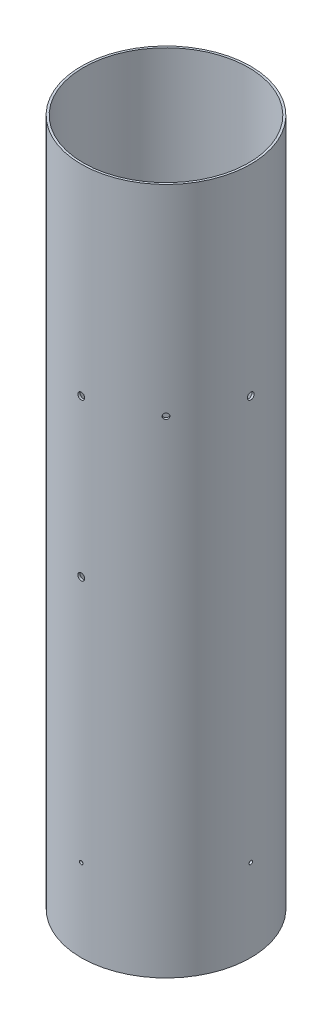
SolidWorks part; units mm, degrees
ref_plane "Front Plane" through (0, 0, 0) normal (0, 0, 1) x (1, 0, 0)
ref_plane "Top Plane" through (0, 0, 0) normal (0, 1, 0) x (1, 0, 0)
ref_plane "Right Plane" through (0, 0, 0) normal (1, 0, 0) x (0, 0, -1)
sketch "Sketch2" plane through (0, 0, 0) normal (0, 1, 0) x (1, 0, 0)
  circle A0 centre (0, 0) radius 76.3651
  circle A1 centre (0, 0) radius 78.359
  dimension "D1" = 152.7302
  dimension "D2" = 156.718
extrude "Boss-Extrude1" add sketch "Sketch2" along normal blind 635
sketch "Sketch3" plane through (0, 0, 0) normal (0, 0, 1) x (1, 0, 0)
  circle A0 centre (0, 76.2) radius 1.1906
  dimension "D2" = 2.3813
  dimension "D1" = 76.2
extrude "Cut-Extrude1" [suppressed] cut sketch "Sketch3" against normal through all both and the other way through all
pattern_circular "CirPattern1" [suppressed] count 4 over 360 of bodies 102
sketch "Sketch4" plane through (0, 0, 0) normal (0, 0, 1) x (1, 0, 0)
  circle A0 centre (0, 449.5038) radius 3.175
  dimension "D2" = 6.35
  dimension "D1" = 449.5038
extrude "Cut-Extrude2" cut sketch "Sketch4" against normal through all both and the other way through all
pattern_circular "CirPattern2" count 4 over 360 about axis through (0, 635, 0) along (0, 1, 0) of "Cut-Extrude2"
ref_plane "Plane1" through (55.4082, 0, 55.4082) normal (0.7071, 0, 0.7071) x (0, -1, 0)
sketch "Sketch5" plane through (55.4082, 0, 55.4082) normal (0.7071, 0, 0.7071) x (0, -1, 0)
  circle A0 centre (-449.5038, 0) radius 2.5794
  dimension "D1" = 5.1587
  dimension "D2" = 449.5038
extrude "Cut-Extrude3" cut sketch "Sketch5" against normal up to surface and the other way through all up to face at (-76.3025, 448.7766, 3.0906)
sketch "Sketch6" plane through (0, 0, 0) normal (0, 0, 1) x (1, 0, 0)
  circle A0 centre (0, 304.8) radius 3.175
  dimension "D2" = 304.8
extrude "Cut-Extrude4" cut sketch "Sketch6" against normal through all both and the other way through all
ref_plane "Plane2" through (0, 0, 78.359) normal (0, 0, 1) x (1, 0, 0)
sketch "Sketch7" plane through (0, 0, 78.359) normal (0, 0, 1) x (1, 0, 0)
  point P0 (0, 76.2)
  dimension "D1" = 76.2
hole_wizard "#4 Clearance Hole1" positions "Sketch7" profile "Sketch8" hole size "#4" standard "ANSI Inch"
sketch "Sketch8" plane through (0, 76.2, 78.359) normal (1, 0, 0) x (0, -1, 0)
  line L0 (0, 0) -> (0, 5.8066)
  line L1 (0, 5.8066) -> (1.6319, 4.826)
  line L2 (1.6319, 4.826) -> (1.6319, 0)
  line L5 (1.6319, 0) -> (0, 0)
  line L10 (0, 5.8066) -> (-1.632, 4.826) construction
  line L11 (0, -6.35) -> (0, 107.95) construction
  dimension "Hole Dia." = 3.2639
  dimension "Hole Depth" = 4.826
  dimension "Drill Angle" = 118
pattern_circular "CirPattern3" count 4 every 90 about axis through (0, 0, 0) along (0, 1, 0) of "#4 Clearance Hole1"
equation "\"Shear Pin Dia\"= 3 / 32"
equation "\"Shear Pin Offset\"= 3"
equation "\"D1@Sketch3\"=\"Shear Pin Offset\""
equation "\"D2@Sketch3\"=\"Shear Pin Dia\""
equation "\"Bulkhead Screw Dia\"= 1 / 4"
equation "\"Bulkhead Screw Offset\"= 17.697"
equation "\"D1@Sketch4\"=\"Bulkhead Screw Offset\""
equation "\"D2@Sketch4\"=\"Bulkhead Screw Dia\""
equation "\"Rail Button Offset\"= 17.697"
equation "\"Rail Button Dia\"=0.2031"
equation "\"D1@Sketch5\"=\"Rail Button Dia\""
equation "\"Vent Hole Dia\"= 0.25"
equation "\"Vent Hole Offset\"= 12"
equation "\"D2@Sketch6\"=\"Vent Hole Offset\""
equation "\"D1@Sketch7\"=\"Shear Pin Offset\""
